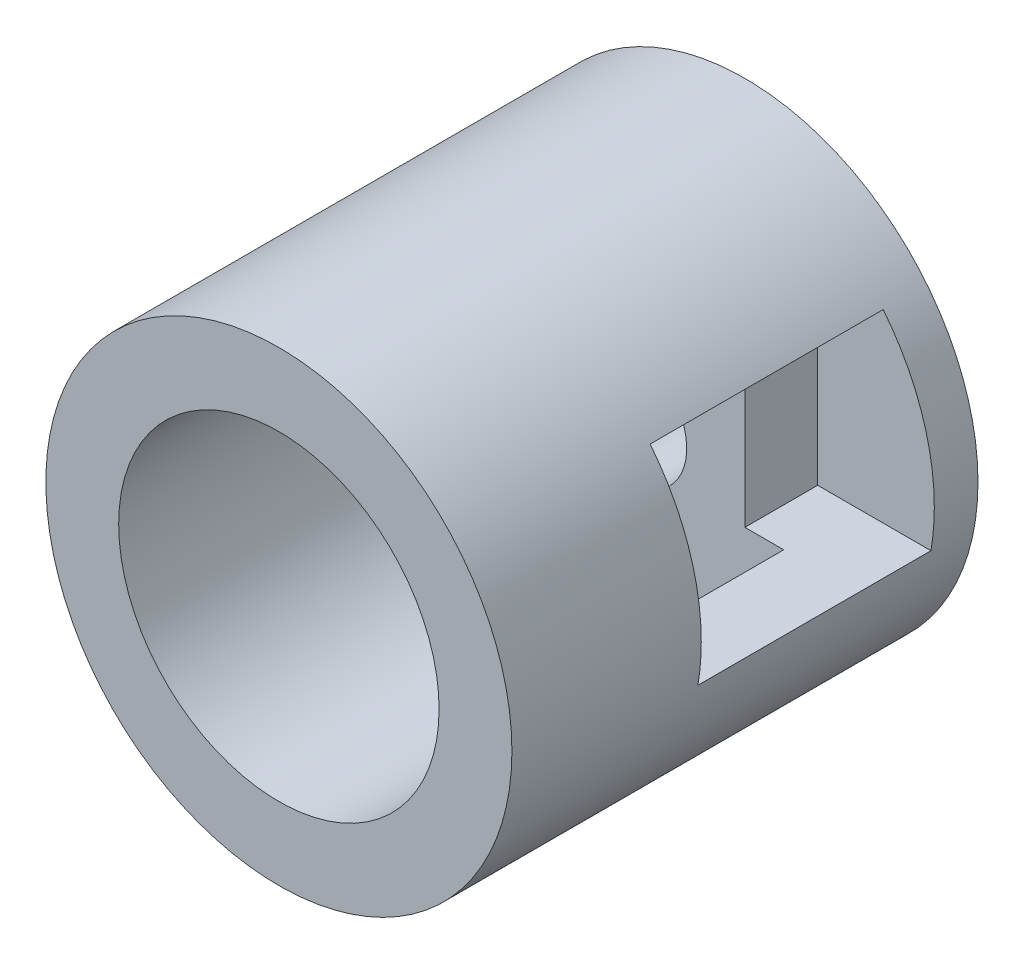
SolidWorks part; units mm, degrees
ref_plane "Front Plane" through (0, 0, 0) normal (0, 0, 1) x (1, 0, 0)
ref_plane "Top Plane" through (0, 0, 0) normal (0, 1, 0) x (1, 0, 0)
ref_plane "Right Plane" through (0, 0, 0) normal (1, 0, 0) x (0, 0, -1)
sketch "Sketch1" plane through (0, 0, 0) normal (0, 0, 1) x (1, 0, 0)
  circle A0 centre (0, 0) radius 4
  dimension "D1" = 8
extrude "Boss-Extrude1" add sketch "Sketch1" against normal blind 6
sketch "Sketch2" plane through (0, 0, -6) normal (0, 0, -1) x (-1, 0, 0)
  line L0 (0, 0) -> (-4, 0) construction
  line L1 (-4, 0) -> (4, 0) construction
  circle A0 centre (0, 0) radius 4 construction
  circle A1 centre (0, 0) radius 2.75
  dimension "D1" = 5.5
extrude "Cut-Extrude1" cut sketch "Sketch2" against normal blind 6
sketch "Sketch3" plane through (0, 0, -6) normal (0, 0, -1) x (-1, 0, 0)
  circle A0 centre (0, 0) radius 4
  dimension "D1" = 8
extrude "Boss-Extrude2" add sketch "Sketch3" along normal blind 2
sketch "Sketch4" plane through (0, 0, -8) normal (0, 0, -1) x (-1, 0, 0)
  circle A0 centre (0, 0) radius 1
  dimension "D1" = 2
extrude "Cut-Extrude2" cut sketch "Sketch4" against normal blind 2
sketch3d "3DSketch1"
  point P0 (3.9179, 0.806, 2.6575)
sketch3d "3DSketch2"
  point P0 (3.9756, 0.4409, 2.9382)
sketch3d "3DSketch3"
  point P0 (3.9987, 0.1009, -3.3088)
ref_plane "Plane3" through (3.9987, 0, 0) normal (1, 0, 0) x (0, 0, -1)
sketch "Sketch9" plane through (3.9987, 0, 0) normal (1, 0, 0) x (0, 0, -1)
  line L0 (8, 4) -> (0, 4) construction
  line L1 (3.25, 2.5) -> (7.25, 2.5)
  line L2 (3.25, 2.5) -> (3.25, -0.675)
  line L3 (3.25, -0.675) -> (7.25, -0.675)
  line L4 (7.25, 2.5) -> (7.25, -0.675)
  line L5 (0, 4) -> (0, -4) construction
  dimension "D1" = 4
  dimension "D2" = 3.175
  dimension "D3" = 1.5
  dimension "D4" = 3.25
extrude "Cut-Extrude8" cut sketch "Sketch9" against normal blind 2 and the other way blind 2 contours L2 L1 L4 L3
